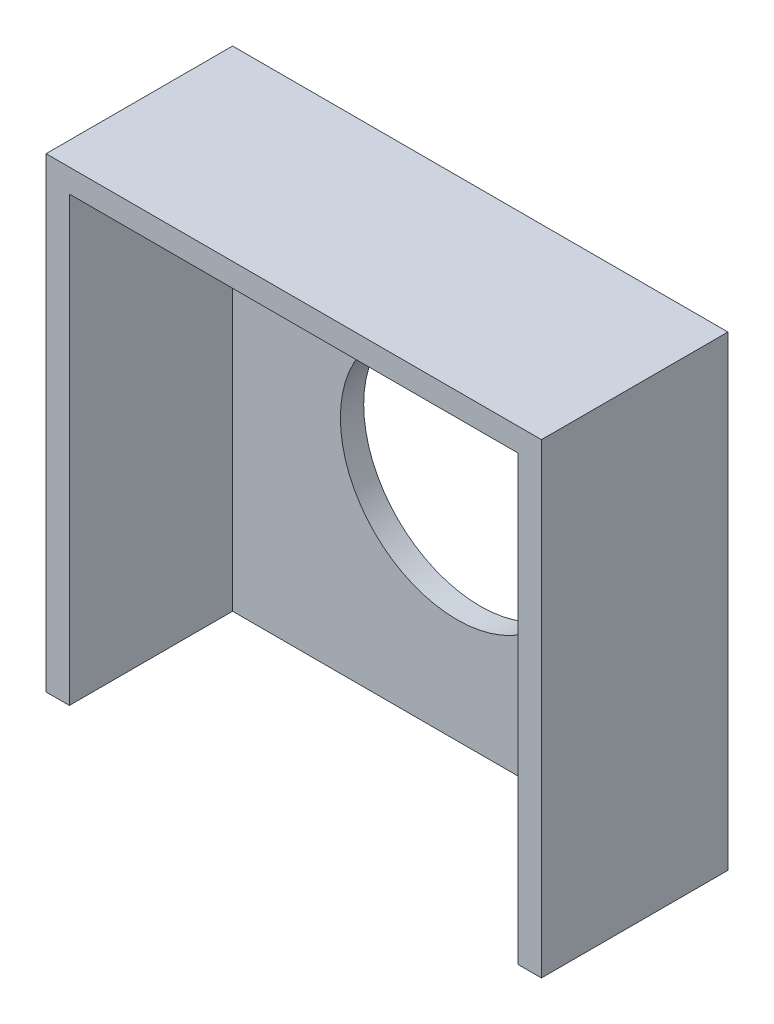
SolidWorks part; units mm, degrees
ref_plane "Front Plane" through (0, 0, 0) normal (0, 0, 1) x (1, 0, 0)
ref_plane "Top Plane" through (0, 0, 0) normal (0, 1, 0) x (1, 0, 0)
ref_plane "Right Plane" through (0, 0, 0) normal (1, 0, 0) x (0, 0, -1)
sketch "Sketch1" plane through (0, 0, 0) normal (0, 0, 1) x (1, 0, 0)
  line L1 (-19.25, 19) -> (19.25, 19)
  line L2 (-19.25, 19) -> (-19.25, -19)
  line L3 (-19.25, -19) -> (19.25, -19)
  line L4 (19.25, 19) -> (19.25, -19)
  line L5 (-19.25, 19) -> (19.25, -19) construction
  line L6 (-19.25, -19) -> (19.25, 19) construction
  circle A0 centre (0, 0) radius 10
  point P0 (0, 0)
  dimension "D3" = 20
  dimension "D1" = 38.5
  dimension "D2" = 38
extrude "Boss-Extrude1" add sketch "Sketch1" along normal blind 2 contours L1 L2 L3 | L1 L3 A0 | L1 L3 L4 | L1 region at (0, 18.4591, 0)
sketch "Sketch2" plane through (0, 0, 2) normal (0, 0, 1) x (1, 0, 0)
  line L0 (-19.25, -19) -> (-21.25, -19)
  line L1 (-21.25, -19) -> (-21.25, 21)
  line L2 (-21.25, 21) -> (21.25, 21)
  line L4 (19.25, -19) -> (21.25, -19)
  line L6 (19.25, -19) -> (19.25, 19)
  line L7 (19.25, 19) -> (-19.25, 19)
  line L8 (0, 40.5) -> (0, -19) construction
  line L9 (-19.25, 19) -> (-19.25, -19)
  line L10 (-19.25, -19) -> (19.25, -19) construction
  line L11 (-19.25, -19) -> (19.25, -19)
  line L12 (19.25, -19) -> (19.25, 19)
  line L13 (19.25, 19) -> (-19.25, 19)
  line L14 (-19.25, 19) -> (-19.25, -19)
  line L15 (-19.25, -19) -> (19.25, -19)
  line L16 (21.25, -19) -> (21.25, 21)
  point P10 (0, 21)
  line M17 (19.25, -19) -> (19.25, 19)
  line M18 (19.25, 19) -> (-19.25, 19)
  line M22 (19.25, 19) -> (-19.25, 19)
  line M23 (-19.25, 19) -> (-19.25, -19)
  dimension "D1" = 0
  dimension "D2" = 2
  dimension "D3" = 2
extrude "Boss-Extrude2" add sketch "Sketch2" along normal blind 14 and the other way up to surface (2 mm away) contours L8 M23 M22 | L8 M18 M17 region at (-20.25, -18.4164, 2) other way up to face at (10, 0, 0)
